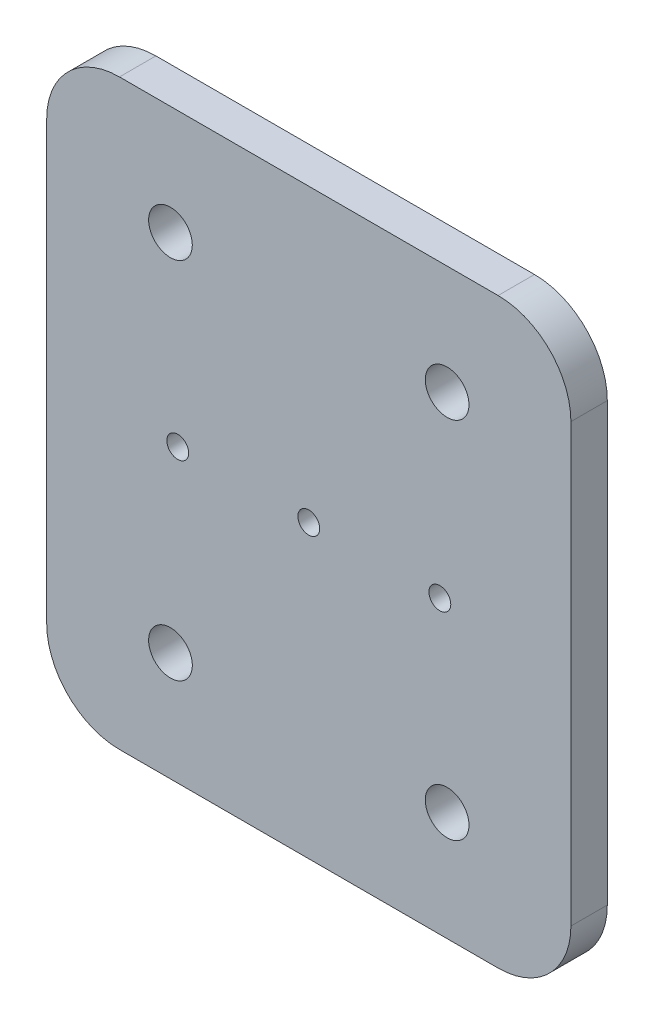
SolidWorks part; units mm, degrees
ref_plane "Front Plane" through (0, 0, 0) normal (0, 0, 1) x (1, 0, 0)
ref_plane "Top Plane" through (0, 0, 0) normal (0, 1, 0) x (1, 0, 0)
ref_plane "Right Plane" through (0, 0, 0) normal (1, 0, 0) x (0, 0, -1)
sketch "Sketch1" plane through (0, 0, 0) normal (0, 0, 1) x (1, 0, 0)
  line L0 (-114.9695, 0) -> (114.9695, 0) construction
  line L1 (0, 64.3489) -> (0, -95.298) construction
  line L3 (36, -40) -> (-36, -40)
  line L4 (36, -40) -> (36, 40)
  line L5 (36, 40) -> (-36, 40)
  line L6 (-36, -40) -> (-36, 40)
  line L7 (36, -40) -> (-36, 40) construction
  line L8 (36, 40) -> (-36, -40) construction
  line L9 (-12.5, 40) -> (-12.5, -40) construction
  line L11 (12.5, 40) -> (12.5, -40) construction
  line L12 (-36, 10) -> (36, 10) construction
  circle A1 centre (-19, 25) radius 6.5 construction
  circle A2 centre (-19, 25) radius 9.5 construction
  circle A3 centre (-19, 25) radius 3
  circle A4 centre (19, 25) radius 3
  circle A5 centre (19, 25) radius 9.5 construction
  circle A6 centre (19, 25) radius 6.5 construction
  circle A7 centre (19, -25) radius 3
  circle A8 centre (-19, -25) radius 3
  circle A9 centre (-19, -25) radius 6.5 construction
  circle A10 centre (-19, -25) radius 9.5 construction
  circle A11 centre (19, -25) radius 9.5 construction
  circle A12 centre (19, -25) radius 6.5 construction
  circle A13 centre (0, 0) radius 1.5
  circle A14 centre (-18, 0) radius 1.5
  circle A15 centre (18, 0) radius 1.5
  point P4 (0, 0)
  point P6 (0, 0)
  dimension "D5" = 13
  dimension "D6" = 3
  dimension "D7" = 6
  dimension "D9" = 3
  dimension "D10" = 18
  dimension "D1" = 80
  dimension "D2" = 72
  dimension "D3" = 12.5
  dimension "D4" = 10
  dimension "D8" = 25
extrude "Boss-Extrude1" add sketch "Sketch1" along normal blind 5
fillet "Fillet1" radius 10 4 edges at (36, -40, 2.5) (-36, -40, 2.5) (-36, 40, 2.5) (36, 40, 2.5)
